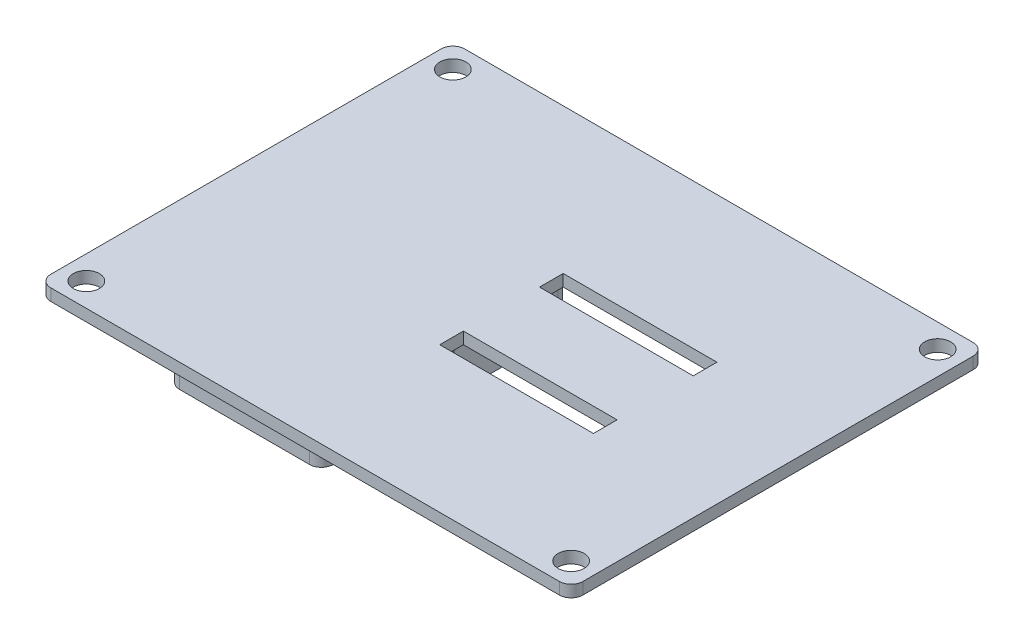
SolidWorks part; units mm, degrees
ref_plane "Front Plane" through (0, 0, 0) normal (0, 0, 1) x (1, 0, 0)
ref_plane "Top Plane" through (0, 0, 0) normal (0, 1, 0) x (1, 0, 0)
ref_plane "Right Plane" through (0, 0, 0) normal (1, 0, 0) x (0, 0, -1)
sketch "Sketch1" plane through (0, 0, 0) normal (0, 1, 0) x (1, 0, 0)
  line L1 (-57.15, -44.45) -> (57.15, -44.45)
  line L2 (-57.15, -44.45) -> (-57.15, 44.45)
  line L3 (-57.15, 44.45) -> (57.15, 44.45)
  line L4 (57.15, -44.45) -> (57.15, 44.45)
  line L5 (-57.15, -44.45) -> (57.15, 44.45) construction
  line L6 (-57.15, 44.45) -> (57.15, -44.45) construction
  point P0 (0, 0)
  dimension "D1" = 88.9
  dimension "D2" = 114.3
extrude "Boss-Extrude2" add sketch "Sketch1" along normal blind 2.54
sketch "Sketch2" plane through (0, 0, 0) normal (0, -1, 0) x (-1, 0, 0)
  line L1 (-52.07, 39.37) -> (52.07, 39.37)
  line L2 (-52.07, 39.37) -> (-52.07, -39.37)
  line L3 (-52.07, -39.37) -> (52.07, -39.37)
  line L4 (52.07, 39.37) -> (52.07, -39.37)
  line L5 (-52.07, 39.37) -> (52.07, -39.37) construction
  line L6 (-52.07, -39.37) -> (52.07, 39.37) construction
  circle A0 centre (52.07, 39.37) radius 2.794
  circle A1 centre (52.07, -39.37) radius 2.794
  circle A2 centre (-52.07, -39.37) radius 2.794
  circle A3 centre (-52.07, 39.37) radius 2.794
  point P0 (0, 0)
  dimension "D3" = 5.588
  dimension "D4" = 5.588
  dimension "D5" = 5.588
  dimension "D6" = 5.588
  dimension "D1" = 104.14
  dimension "D2" = 78.74
extrude "Cut-Extrude1" cut sketch "Sketch2" against normal blind 5.08 contours A0 | A1 | A2 | A3
sketch "Sketch8" plane through (0, 0, 0) normal (0, -1, 0) x (-1, 0, 0)
  line L1 (48.5659, -25.4) -> (15.5459, -25.4)
  line L2 (48.5659, -25.4) -> (48.5659, 27.94)
  line L3 (48.5659, 27.94) -> (15.5459, 27.94)
  line L4 (15.5459, -25.4) -> (15.5459, 27.94)
  line L5 (48.5659, -25.4) -> (15.5459, 27.94) construction
  line L6 (48.5659, 27.94) -> (15.5459, -25.4) construction
  point P0 (32.0559, 1.27)
  dimension "D1" = 33.02
  dimension "D2" = 53.34
sketch "Sketch9" plane through (0, 0, 0) normal (0, -1, 0) x (-1, 0, 0)
  line L0 (0, 44.45) -> (0, -44.45) construction
  line L1 (-57.15, 44.45) -> (57.15, 44.45) construction
  line L2 (57.15, -44.45) -> (-57.15, -44.45) construction
  line L3 (-57.15, 0) -> (57.15, 0) construction
  line L4 (-57.15, -44.45) -> (-57.15, 44.45) construction
  line L5 (57.15, 44.45) -> (57.15, -44.45) construction
  line L6 (2.2645, -13.2599) -> (2.2645, -8.1799)
  line L7 (-30.7555, 13.2599) -> (2.2645, 13.2599)
  line L8 (-30.7555, 13.2599) -> (-30.7555, 8.1799)
  line L9 (-30.7555, 8.1799) -> (2.2645, 8.1799)
  line L10 (2.2645, 13.2599) -> (2.2645, 8.1799)
  line L11 (-30.7555, 13.2599) -> (2.2645, 8.1799) construction
  line L12 (-30.7555, 8.1799) -> (2.2645, 13.2599) construction
  line L13 (-30.7555, -8.1799) -> (2.2645, -8.1799)
  line L14 (-30.7555, -13.2599) -> (-30.7555, -8.1799)
  line L15 (-30.7555, -13.2599) -> (2.2645, -13.2599)
  point P12 (-14.2455, 10.7199)
  dimension "D1" = 33.02
  dimension "D2" = 5.08
extrude "Cut-Extrude5" cut sketch "Sketch9" against normal blind 6.35
extrude "Boss-Extrude4" add sketch "Sketch8" along normal blind 21.59 separate body
shell "Shell4" thickness 2.54 removed face at (-32.0559, -21.59, -1.27)
sketch "Sketch13" plane through (0, 0, -27.94) normal (0, 0, -1) x (-1, 0, 0)
  line L0 (32.0559, 0) -> (32.0559, -21.59) construction
  line L1 (48.5659, 0) -> (15.5459, 0) construction
  line L2 (48.5659, -21.59) -> (15.5459, -21.59) construction
  line L3 (48.5659, -10.795) -> (15.5459, -10.795) construction
  line L4 (48.5659, -21.59) -> (48.5659, 0) construction
  line L5 (15.5459, -21.59) -> (15.5459, 0) construction
  line L7 (44.3624, -3.7461) -> (19.7495, -3.7461)
  line L8 (44.3624, -3.7461) -> (44.3624, -17.8439)
  line L9 (44.3624, -17.8439) -> (19.7495, -17.8439)
  line L10 (19.7495, -3.7461) -> (19.7495, -17.8439)
  line L11 (44.3624, -3.7461) -> (19.7495, -17.8439) construction
  line L12 (44.3624, -17.8439) -> (19.7495, -3.7461) construction
  point P12 (32.0559, -10.795)
extrude "Cut-Extrude6" cut sketch "Sketch13" against normal blind 5.08
fillet "Fillet5" radius 2.54 1 edges at (-19.7495, -17.8439, -26.67)
fillet "Fillet6" radius 2.54 1 edges at (-19.7495, -3.7461, -26.67)
fillet "Fillet7" radius 2.54 1 edges at (-44.3624, -3.7461, -26.67)
fillet "Fillet8" radius 2.54 1 edges at (-44.3624, -17.8439, -26.67)
fillet "Fillet1" radius 2.54 1 edges at (57.15, 1.27, 44.45)
fillet "Fillet2" radius 2.54 1 edges at (-57.15, 1.27, -44.45)
fillet "Fillet3" radius 2.54 1 edges at (-57.15, 1.27, 44.45)
fillet "Fillet4" radius 2.54 1 edges at (57.15, 1.27, -44.45)
fillet "Fillet9" radius 2.54 1 edges at (-15.5459, -10.795, -27.94)
fillet "Fillet10" radius 2.54 1 edges at (-15.5459, -10.795, 25.4)
fillet "Fillet11" radius 2.54 1 edges at (-48.5659, -10.795, 25.4)
fillet "Fillet12" radius 2.54 1 edges at (-48.5659, -10.795, -27.94)
sketch "Sketch17" plane through (0, 0, 0) normal (0, -1, 0) x (-1, 0, 0)
  line L0 (-57.15, 37.465) -> (57.15, 37.465) construction
  line L1 (-57.15, -41.91) -> (-57.15, 41.91) construction
  line L2 (57.15, 41.91) -> (57.15, -41.91) construction
  line L3 (-54.61, 44.45) -> (54.61, 44.45) construction
  line L5 (-37.0749, 37.465) -> (8.6451, 37.465) construction
  line L6 (-37.0749, 37.465) -> (-37.0749, -8.255) construction
  line L7 (-37.0749, -8.255) -> (8.6451, -8.255) construction
  line L8 (8.6451, 37.465) -> (8.6451, -8.255) construction
  line L9 (-37.0749, 37.465) -> (8.6451, -8.255) construction
  line L10 (-37.0749, -8.255) -> (8.6451, 37.465) construction
  circle A0 centre (8.6451, -8.255) radius 3.175
  circle A1 centre (8.6451, 37.465) radius 3.175
  circle A2 centre (-37.0749, 37.465) radius 3.175
  circle A3 centre (-37.0749, -8.255) radius 3.175
  point P12 (-14.2149, 14.605)
  point P18 (-37.0749, -8.255)
  point P19 (-37.0749, 37.465)
  point P20 (8.6451, 37.465)
  point P21 (8.6451, -8.255)
  point P22 (-37.0749, -8.255)
  point P23 (-37.0749, 37.465)
  point P24 (8.6451, -8.255)
  point P25 (8.6451, 37.465)
  dimension "D4" = 6.35
  dimension "D5" = 6.35
  dimension "D6" = 6.35
  dimension "D7" = 6.35
  dimension "D1" = 6.985
  dimension "D2" = 45.72
  dimension "D3" = 45.72
extrude "Boss-Extrude5" add sketch "Sketch17" along normal blind 7.62
sketch "Sketch18" plane through (0, -7.62, 0) normal (0, -1, 0) x (1, 0, 0)
  circle A0 centre (37.0749, 8.255) radius 1.651
  circle A1 centre (37.0749, -37.465) radius 1.651
  circle A2 centre (-8.6451, -37.465) radius 1.651
  circle A3 centre (-8.6451, 8.255) radius 1.651
  point P0 (-8.6451, 8.255)
  point P1 (-8.6451, -37.465)
  point P3 (37.0749, -37.465)
  point P5 (37.0749, 8.255)
  dimension "D1" = 3.302
  dimension "D2" = 3.302
  dimension "D3" = 3.302
  dimension "D4" = 3.302
extrude "Cut-Extrude7" cut sketch "Sketch18" against normal blind 5.08 draft 2 contours A0 | A1 | A2 | A3
